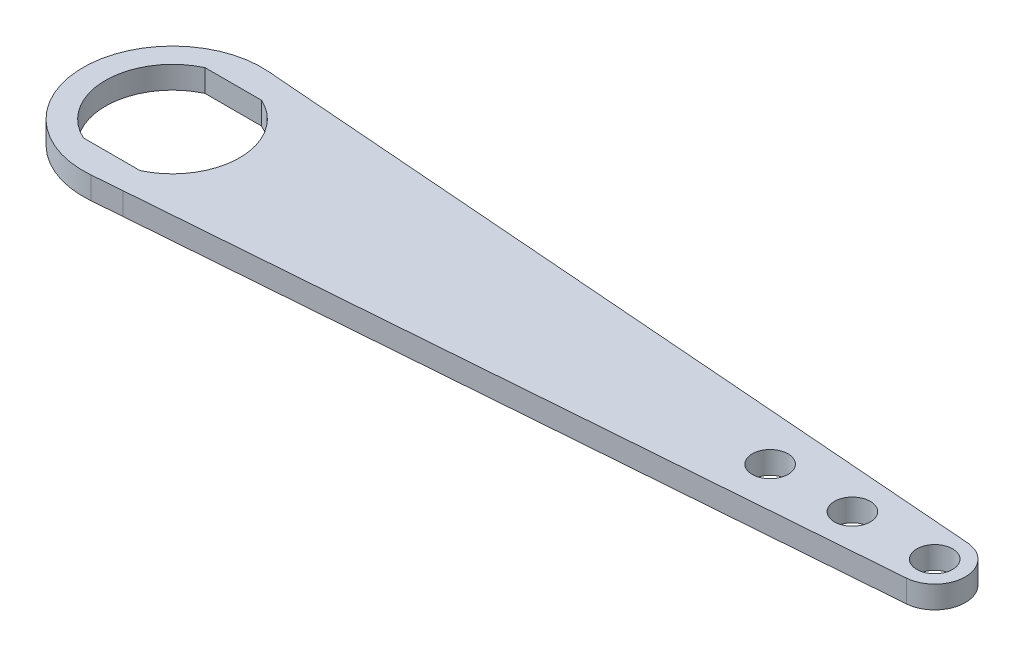
SolidWorks part; units mm, degrees
material "AISI 4130 Steel, annealed at 865C"
ref_plane "Front Plane" through (0, 0, 0) normal (0, 0, 1) x (1, 0, 0)
ref_plane "Top Plane" through (0, 0, 0) normal (0, 1, 0) x (1, 0, 0)
ref_plane "Right Plane" through (0, 0, 0) normal (1, 0, 0) x (0, 0, -1)
sketch "Sketch1" plane through (0, 0, 0) normal (0, 1, 0) x (1, 0, 0)
  line L3 (108.5391, 4.3352) -> (5.2635, 12.3186)
  line L4 (-55, 0) -> (55, 0) construction
  line L5 (108.5391, -4.3352) -> (5.2635, -12.3186)
  arc A2 (1.0518, -12.6564) -> (1.0518, 12.6564) centre (0, 0) cw
  arc A3 (108.5391, 4.3352) -> (108.5391, -4.3352) centre (108.204, 0) cw
  circle A4 centre (108.204, 0) radius 2.54
  circle A5 centre (96.52, 0) radius 2.54
  circle A6 centre (84.836, 0) radius 2.54
  arc A8 (5.2635, 12.3186) -> (1.0518, 12.6564) centre (61.7867, 743.5167) cw
  arc A9 (5.2635, -12.3186) -> (1.0518, -12.6564) centre (61.7867, -743.5167) ccw
  dimension "D1" = 5.08
  dimension "D3" = 12.7
  dimension "D4" = 5.08
  dimension "D5" = 11.684
  dimension "D2" = 96.52
  dimension "D6" = 11.684
sketch "Sketch3" plane through (0, 0, 0) normal (0, 1, 0) x (1, 0, 0)
  line L0 (-4.0181, 8.636) -> (4.0181, 8.636)
  line L1 (4.0181, -8.636) -> (-4.0181, -8.636)
  arc A1 (-4.0181, 8.636) -> (-4.0181, -8.636) centre (0, 0) ccw
  arc A2 (4.0181, 8.636) -> (4.0181, -8.636) centre (0, 0) cw
  point P3 (0, 8.636)
  dimension "D1" = 8.0362
extrude "Boss-Extrude1" add sketch "Sketch1" along normal blind 3.175
extrude "Cut-Extrude1" cut sketch "Sketch3" against normal through all both and the other way through all
sketch "Sketch6" plane through (0, 0, 0) normal (0, -1, 0) x (1, 0, 0)
  line L0 (82.296, 0) -> (87.376, 0)
  line L1 (93.98, 0) -> (99.06, 0)
  line L2 (105.664, 0) -> (110.744, 0)
  line L3 (84.836, 2.54) -> (84.836, -2.54)
  circle A0 centre (84.836, 0) radius 2.54 construction
  circle A1 centre (96.52, 0) radius 2.54 construction
  circle A2 centre (108.204, 0) radius 2.54 construction
split line "Split Line1"
sketch "Sketch8" plane through (0, 0, 0) normal (0, -1, 0) x (1, 0, 0)
  line L0 (0, 0) -> (0, 4.0363)
